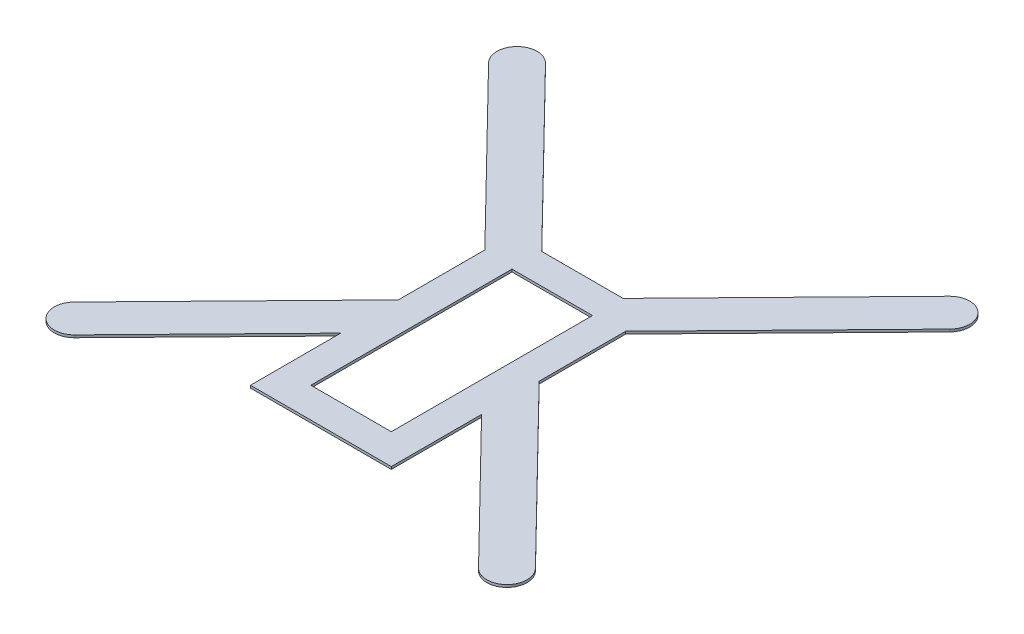
SolidWorks part; units mm, degrees
ref_plane "Front Plane" through (0, 0, 0) normal (0, 0, 1) x (1, 0, 0)
ref_plane "Top Plane" through (0, 0, 0) normal (0, 1, 0) x (1, 0, 0)
ref_plane "Right Plane" through (0, 0, 0) normal (1, 0, 0) x (0, 0, -1)
sketch "Sketch2" plane through (0, 0, 0) normal (0, 1, 0) x (1, 0, 0)
  line L0 (-136.525, 139.7) -> (136.525, -139.7) construction
  line L1 (-127.4421, 148.5764) -> (-25.6822, 44.45)
  line L2 (-145.6079, 130.8236) -> (-44.45, 27.3132)
  line L3 (-136.525, -139.7) -> (136.525, 139.7) construction
  line L4 (-145.6079, -130.8236) -> (-44.45, -27.3132)
  line L5 (-127.4421, -148.5764) -> (-44.45, -63.6543)
  line L7 (-25.4, -101.6) -> (25.4, -101.6)
  line L8 (-25.4, -101.6) -> (-25.4, 25.4)
  line L9 (-25.4, 25.4) -> (25.4, 25.4)
  line L10 (25.4, -101.6) -> (25.4, 25.4)
  line L11 (-25.4, -101.6) -> (25.4, 25.4) construction
  line L12 (-25.4, 25.4) -> (25.4, -101.6) construction
  line L13 (44.45, -120.65) -> (44.45, -63.6543)
  line L14 (-44.45, -120.65) -> (44.45, -120.65)
  line L15 (-44.45, -120.65) -> (-44.45, -63.6543)
  line L16 (44.45, -63.6543) -> (127.4421, -148.5764)
  line L17 (-25.6822, 44.45) -> (25.6822, 44.45)
  line L18 (-44.45, 44.45) -> (44.45, 44.45) construction
  line L19 (-44.45, -120.65) -> (-44.45, 44.45) construction
  line L20 (25.6822, 44.45) -> (127.4421, 148.5764)
  line L21 (44.45, 27.3132) -> (145.6079, 130.8236)
  line L22 (44.45, -27.3132) -> (145.6079, -130.8236)
  line L23 (43.4398, 44.45) -> (44.45, 44.45)
  line L24 (44.45, -120.65) -> (44.45, 44.45) construction
  line L25 (44.45, -27.3132) -> (44.45, 27.3132)
  line L26 (-44.45, -27.3132) -> (-44.45, 27.3132)
  arc A0 (-127.4421, 148.5764) -> (-145.6079, 130.8236) centre (-136.525, 139.7) ccw
  arc A1 (127.4421, -148.5764) -> (145.6079, -130.8236) centre (136.525, -139.7) ccw
  arc A2 (-145.6079, -130.8236) -> (-127.4421, -148.5764) centre (-136.525, -139.7) ccw
  arc A3 (145.6079, 130.8236) -> (127.4421, 148.5764) centre (136.525, 139.7) ccw
  point P2 (0, 0)
  point P9 (0, 0)
  point P15 (0, 0)
  point P18 (0, -38.1)
  point P29 (0, 0)
  point P34 (44.45, -27.3132)
  point P35 (20.1707, 44.45)
  point P37 (0, 44.45)
  point P38 (-141.068, -122.8515)
  point P39 (0, 0)
  point P40 (0, 0)
  point P42 (0, 0)
  point P43 (0, 0)
  point P44 (0, 0)
  dimension "D3" = 12.7
  dimension "D1" = 273.05
  dimension "D2" = 279.4
  dimension "D4" = 50.8
  dimension "D5" = 127
  dimension "D6" = 101.6
  dimension "D7" = 19.05
extrude "Boss-Extrude1" add sketch "Sketch2" along normal mid plane 1.5875 contours L21 A3 L20 L17 L1 A0 L2 L26 L4 A2 L5 L15 L14 L13 L16 A1 L22 L25 L10 L7 L8 L9 region at (-79.613, 0, -93.5317)
